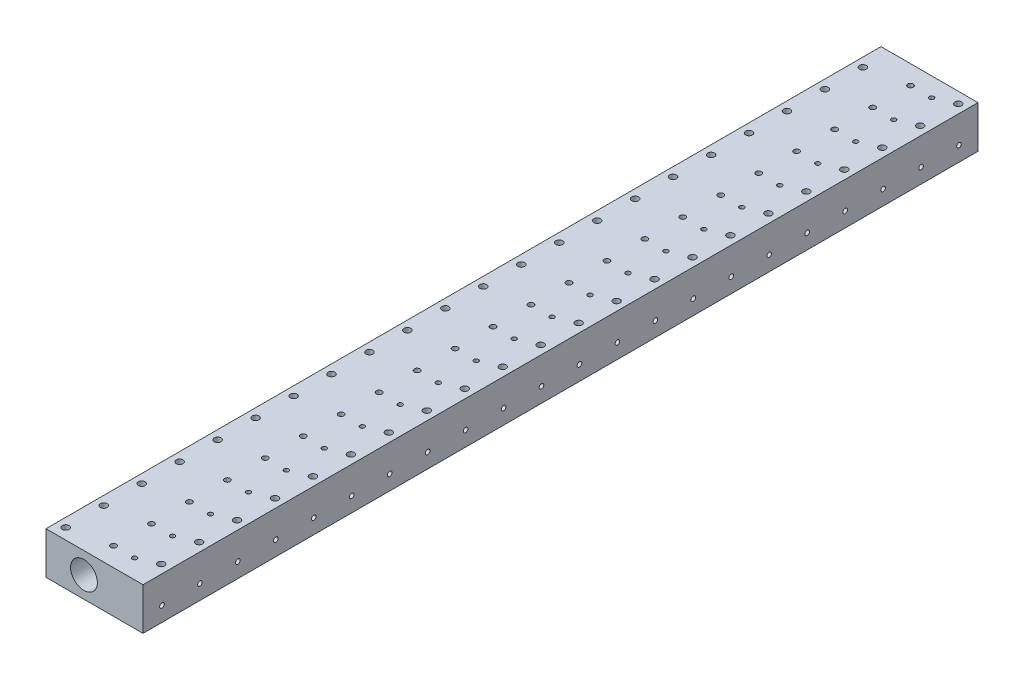
SolidWorks part; units mm, degrees
ref_plane "Front Plane" through (0, 0, 0) normal (0, 0, 1) x (1, 0, 0)
ref_plane "Top Plane" through (0, 0, 0) normal (0, 1, 0) x (1, 0, 0)
ref_plane "Right Plane" through (0, 0, 0) normal (1, 0, 0) x (0, 0, -1)
sketch "Sketch1" plane through (0, 0, 0) normal (0, 0, 1) x (1, 0, 0)
  line L1 (-11.5, -5) -> (11.5, -5)
  line L2 (-11.5, -5) -> (-11.5, 5)
  line L3 (-11.5, 5) -> (11.5, 5)
  line L4 (11.5, -5) -> (11.5, 5)
  line L5 (-11.5, -5) -> (11.5, 5) construction
  line L6 (-11.5, 5) -> (11.5, -5) construction
  point P0 (0, 0)
  dimension "D1" = 23
  dimension "D2" = 10
extrude "Boss-Extrude1" add sketch "Sketch1" against normal blind 198
hole_wizard "#55 (0.052) Diameter Hole1" positions "Sketch2" profile "Sketch4" hole size "#55" standard "ANSI Inch"
sketch "Sketch2" plane through (0, 5, 0) normal (0, 1, 0) x (1, 0, 0)
  line L0 (11.5, 0) -> (-11.5, 0) construction
  point P0 (0, 4.5)
  dimension "D1" = 4.5
sketch "Sketch4" plane through (0, 5, -4.5) normal (1, 0, 0) x (0, 0, 1)
  line L0 (0, 0) -> (0, 7.3968)
  line L1 (0, 7.3968) -> (0.6604, 7)
  line L2 (0.6604, 7) -> (0.6604, 0)
  line L5 (0.6604, 0) -> (0, 0)
  line L10 (0, 7.3968) -> (-0.6604, 7) construction
  line L11 (0, -6.35) -> (0, 107.95) construction
  dimension "Hole Dia." = 1.3208
  dimension "Hole Depth" = 7
  dimension "Drill Angle" = 118
sketch "Sketch5" plane through (0, 0, 0) normal (0, 0, 1) x (1, 0, 0)
  circle A0 centre (-2.5, 0) radius 3.175
  dimension "D2" = 6.35
  dimension "D1" = 2.5
extrude "Cut-Extrude1" cut sketch "Sketch5" against normal through all
hole_wizard "M2 Tapped Hole1" positions "Sketch6" profile "Sketch8" tap size "M2" standard "ISO"
sketch "Sketch6" plane through (0, 5, 0) normal (0, 1, 0) x (1, 0, 0)
  line L0 (0, 4.5) -> (5, 4.5) construction
  point P0 (9.4, 6.4)
  point P2 (-9.4, 2.6)
  dimension "D1" = 9.4
  dimension "D2" = 9.4
  dimension "D3" = 1.9
  dimension "D4" = 1.9
sketch "Sketch8" plane through (9.4, 5, -6.4) normal (1, 0, 0) x (0, 0, 1)
  line L0 (0, 0) -> (0, 5.6807)
  line L1 (0, 5.6807) -> (0.8, 5.2)
  line L2 (0.8, 5.2) -> (0.8, 0)
  line L5 (0.8, 0) -> (0, 0)
  line L10 (0, 5.6807) -> (-0.8, 5.2) construction
  line L11 (0, -6.35) -> (0, 107.95) construction
  dimension "Tap Drill Dia." = 1.6
  dimension "Tap Drill Depth" = 5.2
  dimension "Drill Angle" = 118
cosmetic thread "Hole Thread1"
cosmetic thread "Hole Thread2"
hole_wizard "#57 (0.043) Diameter Hole1" positions "Sketch11" profile "Sketch12" hole size "#57" standard "ANSI Inch"
sketch "Sketch11" plane through (11.5, 0, 0) normal (1, 0, 0) x (0, 0, -1)
  line L0 (0, -5) -> (0, 5) construction
  line L1 (198, 5) -> (0, 5) construction
  point P0 (4.5, -1.5)
  dimension "D1" = 4.5
  dimension "D2" = 6.5
sketch "Sketch12" plane through (11.5, -1.5, -4.5) normal (0, 1, 0) x (0, 0, -1)
  line L0 (0, 0) -> (0, 6.3281)
  line L1 (0, 6.3281) -> (0.5461, 6)
  line L2 (0.5461, 6) -> (0.5461, 0)
  line L5 (0.5461, 0) -> (0, 0)
  line L10 (0, 6.3281) -> (-0.5461, 6) construction
  line L11 (0, -6.35) -> (0, 107.95) construction
  dimension "Hole Dia." = 1.0922
  dimension "Hole Depth" = 6
  dimension "Drill Angle" = 118
hole_wizard "#57 (0.043) Diameter Hole2" positions "Sketch13" profile "Sketch14" hole size "#57" standard "ANSI Inch"
sketch "Sketch13" plane through (0, 5, 0) normal (0, 1, 0) x (1, 0, 0)
  line L0 (0, 4.5) -> (5, 4.5)
  point P0 (5, 4.5)
  dimension "D1" = 5
sketch "Sketch14" plane through (5, 5, -4.5) normal (1, 0, 0) x (0, 0, 1)
  line L0 (0, 0) -> (0, 7.8281)
  line L1 (0, 7.8281) -> (0.5461, 7.5)
  line L2 (0.5461, 7.5) -> (0.5461, 0)
  line L5 (0.5461, 0) -> (0, 0)
  line L10 (0, 7.8281) -> (-0.5461, 7.5) construction
  line L11 (0, -6.35) -> (0, 107.95) construction
  dimension "Hole Dia." = 1.0922
  dimension "Hole Depth" = 7.5
  dimension "Drill Angle" = 118
pattern_linear "LPattern1" count 22 spacing 9 along (0, 0, -1) of "#55 (0.052) Diameter Hole1", "M2 Tapped Hole1", "#57 (0.043) Diameter Hole1", "#57 (0.043) Diameter Hole2"
